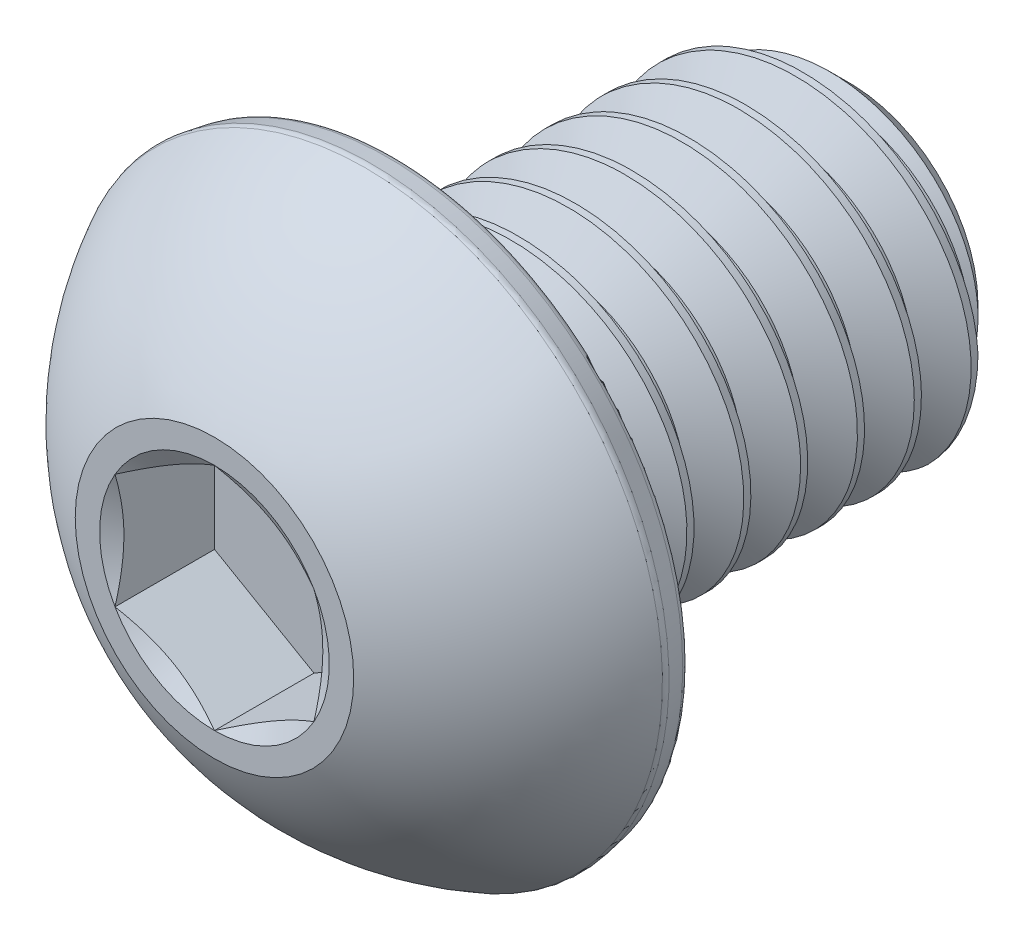
SolidWorks part; units mm, degrees
ref_plane "Front Plane" through (0, 0, 0) normal (0, 0, 1) x (1, 0, 0)
ref_plane "Top Plane" through (0, 0, 0) normal (0, 1, 0) x (1, 0, 0)
ref_plane "Right Plane" through (0, 0, 0) normal (1, 0, 0) x (0, 0, -1)
sketch "Sketch1" plane through (0, 0, 0) normal (1, 0, 0) x (0, 0, -1)
  line L0 (-8.8773, 0) -> (8.8773, 0) construction
  line L1 (-8.8773, 0) -> (-8.8773, 8.3312)
  line L2 (-8.8773, 8.3312) -> (-3.8227, 8.3312)
  line L3 (-3.8227, 8.3312) -> (-3.8227, 4.7625)
  line L4 (-3.8227, 4.7625) -> (8.8773, 4.7625)
  line L5 (8.8773, 4.7625) -> (8.8773, 0)
  point P2 (0, 0)
  point P4 (7.2898, 0)
  point P9 (6.496, 4.7625)
  point P10 (6.496, -4.7625)
  point P11 (8.8773, -4.7625)
  point P15 (-6.0973, 0)
  dimension "Head Height" = 5.0546
  dimension "Head Diameter" = 16.6624
  dimension "Length" = 12.7
  dimension "Screw Size Decimal Equivalent" = 9.525
  dimension "Thread Pitch" = 1.5875
  dimension "D1" = 2.3813
  dimension "D2" = 2.78
sketch "Sketch2" plane through (0, 0, 0) normal (0, 0, 1) x (1, 0, 0)
  line L0 (0, 4.7625) -> (0, 0) construction
  line L1 (0, 3.2079) -> (-2.7781, 1.604)
  line L2 (-2.7781, 1.604) -> (-2.7781, -1.604)
  line L3 (-2.7781, -1.604) -> (0, -3.2079)
  line L4 (0, -3.2079) -> (2.7781, -1.604)
  line L5 (2.7781, -1.604) -> (2.7781, 1.604)
  line L6 (2.7781, 1.604) -> (0, 3.2079)
  circle A0 centre (0, 0) radius 2.7781 construction
  circle A1 centre (0, 0) radius 3.8894
  point P10 (0, 3.8894)
  dimension "D1" = 7.7788
  dimension "Drive Size" = 5.5562
sketch "Sketch3" plane through (0, 0, 0) normal (1, 0, 0) x (0, 0, -1)
  line L0 (-8.8773, 0) -> (-8.8773, 3.8894)
  line L1 (-8.8773, 0) -> (-8.8773, 8.3312) construction
  line L2 (-8.8773, 8.3312) -> (-3.8227, 8.3312) construction
  line L3 (-4.5809, 8.3312) -> (-3.8227, 8.1975)
  line L4 (-3.8227, 8.3312) -> (-3.8227, 4.7625) construction
  line L5 (-3.8227, 8.1975) -> (-3.8227, 4.7625)
  line L6 (-8.8773, 0) -> (8.8773, 0) construction
  line L7 (-8.8773, 0) -> (8.8773, 0)
  line L8 (8.8773, 0) -> (8.8773, 3.5719)
  line L9 (8.8773, 4.7625) -> (8.8773, 0) construction
  line L10 (8.8773, 3.5719) -> (7.6867, 4.7625)
  line L11 (-3.8227, 4.7625) -> (8.8773, 4.7625) construction
  line L12 (7.6867, 4.7625) -> (-3.8227, 4.7625)
  arc A0 (-8.8773, 3.8894) -> (-4.5809, 8.3312) centre (-0.412, 0) cw
  dimension "D1" = 0.7582
  dimension "D2" = 10
  dimension "D3" = 45
  dimension "D4" = 1.1906
revolve "Revolve1" add sketch "Sketch3" angle 360 about L7
sketch "Sketch4" plane through (0, 0, 8.8773) normal (0, 0, 1) x (1, 0, 0)
  line L0 (-2.7781, -1.604) -> (0, -3.2079) construction
  line L1 (-2.7781, 1.604) -> (-2.7781, -1.604) construction
  line L2 (0, 3.2079) -> (-2.7781, 1.604) construction
  line L3 (2.7781, 1.604) -> (0, 3.2079) construction
  line L4 (2.7781, -1.604) -> (2.7781, 1.604) construction
  line L5 (0, -3.2079) -> (2.7781, -1.604) construction
  line L6 (-2.7781, -1.604) -> (0, -3.2079)
  line L7 (-2.7781, 1.604) -> (-2.7781, -1.604)
  line L8 (0, 3.2079) -> (-2.7781, 1.604)
  line L9 (2.7781, 1.604) -> (0, 3.2079)
  line L10 (2.7781, -1.604) -> (2.7781, 1.604)
  line L11 (0, -3.2079) -> (2.7781, -1.604)
extrude "Cut-Extrude1" cut sketch "Sketch4" against normal up to vertex (2.78 mm away) up to point (0, 0, 6.0973)
sketch "Sketch5" plane through (0, 0, 8.8773) normal (0, 0, 1) x (1, 0, 0)
  circle A0 centre (0, 0) radius 3.2079
extrude "Cut-Extrude2" cut sketch "Sketch5" against normal up to vertex (2.78 mm away) draft 60 up to point (0, 0, 6.0973)
fillet "Fillet1" radius 0.2527 2 edges at (8.3312, 0, 4.5809) (8.1975, 0, 3.8227)
split "Split1" bodies to split 106 resulting bodies 107 108 split by face at (7.9854, 0, 3.8227)
sketch "Sketch6" plane through (0, 0, -8.8773) normal (0, 0, -1) x (-1, 0, 0)
  circle A0 centre (0, 0) radius 4.7625 construction
  circle A1 centre (0, 0) radius 4.7625
curve "Helix/Spiral1" pitch 1.5875 height 14.2875 radius 4.7625 centre (0, 0, -8.8773) axis (0, 0, 1) start towards (0, 1, 0)
sketch "Sketch7" plane through (0, 0, 0) normal (1, 0, 0) x (0, 0, -1)
  line L0 (8.7781, 4.9344) -> (9.5718, 3.5595) construction
  line L1 (9.5718, 3.5595) -> (10.3656, 4.9344) construction
  line L2 (10.3656, 4.9344) -> (8.7781, 4.9344) construction
  line L3 (8.8277, 4.8484) -> (10.316, 4.8484)
  line L4 (10.316, 4.8484) -> (9.6711, 3.7314)
  line L5 (9.6711, 3.7314) -> (9.4726, 3.7314)
  line L6 (9.4726, 3.7314) -> (8.8277, 4.8484)
  line L7 (9.5718, 3.7314) -> (9.5718, 3.5595) construction
  line L8 (8.8773, 4.7625) -> (10.2664, 4.7625) construction
  line L9 (9.5718, 4.9344) -> (9.5718, 4.7625) construction
  point P12 (9.5718, 4.8484)
  dimension "D1" = 1.5875
  dimension "D2" = 0.1984
sweep "Cut-Sweep1" cut profiles "Sketch7" path "Helix/Spiral1" align with end faces yes
sketch "Sketch8" plane through (0, 0, 3.8227) normal (0, 0, -1) x (-1, 0, 0)
  circle A0 centre (0, 0) radius 4.9344
extrude "Boss-Extrude1" add sketch "Sketch8" along normal up to vertex (10.3187 mm away) draft 45 up to point (0, 4.7625, -6.496)
equation "\"D1@Sketch1\"=\"Thread Pitch@Sketch1\"*1.5"
equation "\"D2@Sketch1\"=0.55*\"Head Height@Sketch1\""
equation "\"D1@Sketch2\"=\"Drive Size@Sketch2\"*1.4"
equation "\"D1@Sketch3\"=0.15*\"Head Height@Sketch1\""
equation "\"D4@Sketch3\"=0.75*\"Thread Pitch@Sketch1\""
equation "\"D1@Fillet1\"=.05*\"Head Height@Sketch1\""
equation "\"D4@Helix/Spiral1\"=\"Thread Pitch@Sketch1\""
equation "\"D3@Helix/Spiral1\"=\"Length@Sketch1\"+\"Thread Pitch@Sketch1\""
equation "\"D2@Sketch7\"=\"D1@Sketch7\"/8"
equation "\"D1@Sketch7\"=\"Thread Pitch@Sketch1\""
